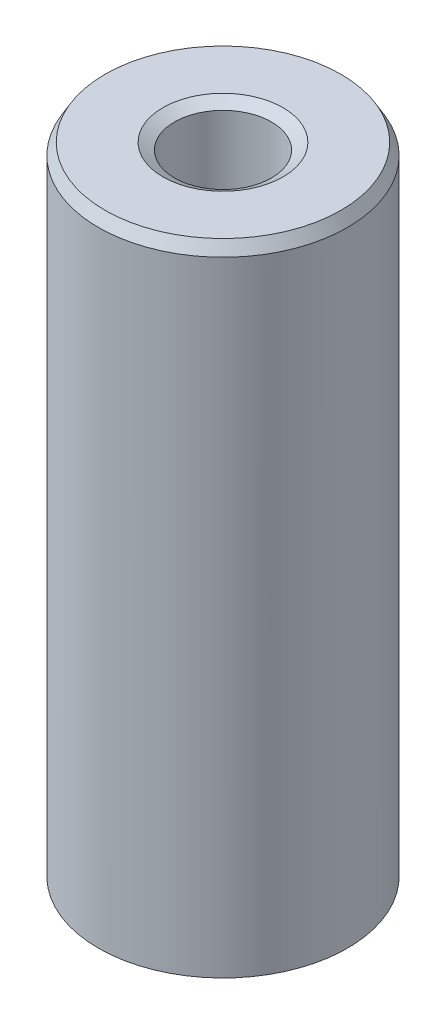
SolidWorks part; units mm, degrees
ref_plane "Front Plane" through (0, 0, 0) normal (0, 0, 1) x (1, 0, 0)
ref_plane "Top Plane" through (0, 0, 0) normal (0, 1, 0) x (1, 0, 0)
ref_plane "Right Plane" through (0, 0, 0) normal (1, 0, 0) x (0, 0, -1)
sketch "Sketch1" plane through (0, 0, 0) normal (0, 1, 0) x (1, 0, 0)
  circle A0 centre (0, 0) radius 35
  dimension "SLEEVE_OD" = 70
extrude "Boss-Extrude1" add sketch "Sketch1" along normal blind 180.4847
sketch "Sketch2" plane through (0, 0, 0) normal (0, 1, 0) x (1, 0, 0)
  circle A0 centre (0, 0) radius 13.6369
  dimension "BORE_D" = 27.2738
extrude "Cut-Extrude1" cut sketch "Sketch2" along normal through all
chamfer "Chamfer1" distance 3.2355 angle 30 4 edges at (0, 180.4847, 13.6369) (0, 0, 13.6369) (0, 0, 35) (0, 180.4847, 35) first distance on face at (0, 180.4847, 13.6369) first distance on face at (0, 0, 13.6369) first distance on face at (0, 180.4847, 35)
